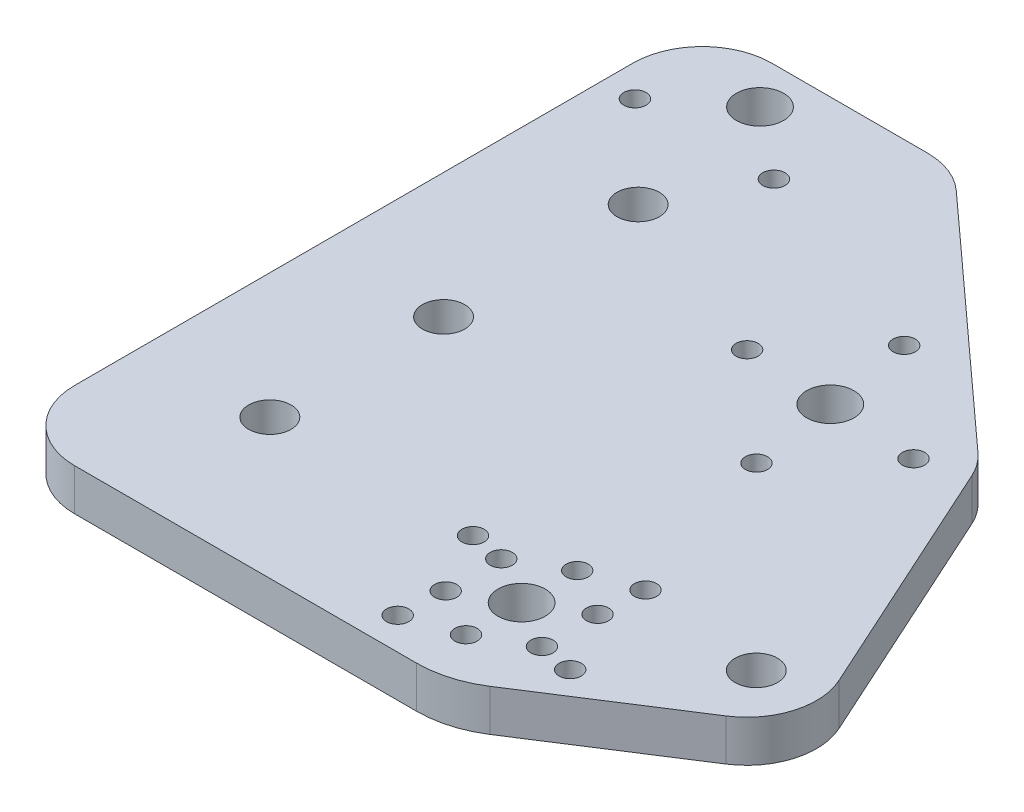
SolidWorks part; units mm, degrees
material "Policarbonato"
ref_plane "Plano frontal" through (0, 0, 0) normal (0, 0, 1) x (1, 0, 0)
ref_plane "Plano superior" through (0, 0, 0) normal (0, 1, 0) x (1, 0, 0)
ref_plane "Plano direito" through (0, 0, 0) normal (1, 0, 0) x (0, 0, -1)
ref_plane "Plano1" through (0, -6, 0) normal (0, -1, 0) x (1, 0, 0)
sketch "Esboço1" plane through (0, -6, 0) normal (0, -1, 0) x (1, 0, 0)
  line L0 (151.2357, -14.2909) -> (167.1948, 20.7865)
  line L1 (163.5005, 33.3393) -> (142.8288, 46.6294)
  line L2 (134.6661, 49.0269) -> (75.4374, 49.0269)
  line L3 (75.4374, 49.0269) -> (75.4374, -53)
  line L4 (78.4374, -56) -> (102.6847, -56)
  line L5 (109.4101, -53.4005) -> (148.859, -17.5502)
  line L6 (134.1775, -0.3541) -> (144.9383, -12.195) construction
  line L7 (144.9383, -12.195) -> (130.1372, -25.6459) construction
  line L8 (130.1372, -25.6459) -> (119.3765, -13.805) construction
  line L9 (119.3765, -13.805) -> (134.1775, -0.3541) construction
  line L10 (134.1775, -0.3541) -> (130.1372, -25.6459) construction
  line L11 (100.0374, -37) -> (80.0374, -53) construction
  line L12 (127.326, 44.4269) -> (146.5154, 38.7906) construction
  line L13 (146.5154, 38.7906) -> (142.0063, 23.4391) construction
  line L14 (142.0063, 23.4391) -> (122.8169, 29.0754) construction
  line L15 (122.8169, 29.0754) -> (127.326, 44.4269) construction
  line L16 (127.326, 44.4269) -> (142.0063, 23.4391) construction
  line L17 (134.6661, 33.933) -> (138.9199, 48.4151) construction
  line L18 (75.4374, -51.3) -> (111.7215, -51.3)
  circle A0 centre (119.3765, -13.805) radius 1.6
  circle A1 centre (146.5154, 38.7906) radius 1.6
  circle A2 centre (142.0063, 23.4391) radius 1.6
  circle A3 centre (159.9953, 25.4877) radius 3.05
  circle A4 centre (100.0374, -37) radius 1.6
  circle A5 centre (100.0374, -53) radius 1.6
  circle A6 centre (80.0374, -37) radius 1.6
  circle A7 centre (80.0374, -53) radius 1.6
  circle A8 centre (122.8169, 29.0754) radius 1.6
  circle A9 centre (127.326, 44.4269) radius 1.6
  circle A10 centre (130.1372, -25.6459) radius 1.6
  circle A11 centre (144.9383, -12.195) radius 1.6
  circle A12 centre (134.1775, -0.3541) radius 1.6
  circle A13 centre (141.5943, 29.933) radius 1.6
  circle A14 centre (134.6661, 25.933) radius 1.6
  circle A15 centre (127.7379, 29.933) radius 1.6
  circle A16 centre (127.7379, 37.933) radius 1.6
  circle A17 centre (134.6661, 41.933) radius 1.6
  circle A18 centre (141.5943, 37.933) radius 1.6
  circle A19 centre (134.6661, 33.933) radius 3.4
  circle A20 centre (132.1574, -13) radius 3.4
  circle A21 centre (90.0374, -45) radius 3.4
  arc A22 (167.1948, 20.7865) -> (163.5005, 33.3393) centre (158.0926, 24.9277) ccw
  arc A23 (142.8288, 46.6294) -> (134.6661, 49.0269) centre (134.6661, 33.933) ccw
  arc A24 (75.4374, -53) -> (78.4374, -56) centre (78.4374, -53) ccw
  arc A25 (102.6847, -56) -> (109.4101, -53.4005) centre (102.6847, -46) ccw
  arc A26 (148.859, -17.5502) -> (151.2357, -14.2909) centre (142.1335, -10.1497) ccw
  arc A27 (107.8564, -51.3) -> (114.5819, -48.7005) centre (107.8564, -41.3) ccw
  point P62 (134.6661, 33.933)
  dimension "D4" = 10
  dimension "D5" = 6.1
  dimension "D8" = 6.8
  dimension "D9" = 3.2
  dimension "D24" = 3
  dimension "D1" = 105.0269
  dimension "D2" = 11
  dimension "D3" = 82.6552
  dimension "D6" = 80.9277
  dimension "D7" = 137.736
  dimension "D10" = 20
  dimension "D11" = 16
  dimension "D12" = 6.6
  dimension "D13" = 52.897
  dimension "D14" = 43
  dimension "D15" = 16
  dimension "D16" = 90.676
  dimension "D17" = 59.2287
  dimension "D18" = 14.6
  dimension "D19" = 8
  dimension "D21" = 26.7
  dimension "D22" = 47.5
  dimension "D23" = 6.6
  dimension "D25" = 4.7
  dimension "D20" = 6
extrude "Ressalto-extrusão1" add sketch "Esboço1" against normal blind 6 contours L18 A27 L5 A26 L0 A22 L1 A23 L2 L3 A21 A19 A17 A15 A13 A11 A9 A3 A1 A0 A2 A4 A6 A8 A10 A12 A14 A16 A18 A20 region at (113.3527, -6, 3.5356)
sketch "Esboço2" plane through (0, -6, 0) normal (0, -1, 0) x (1, 0, 0)
  line L0 (75.4374, 49.0269) -> (75.4374, -51.3) construction
  line L1 (71.813, 11.433) -> (140.3089, 11.433) construction
  circle A0 centre (93.4374, 3.933) radius 3.05
  circle A1 centre (93.4374, -24.067) radius 3.05
  circle A2 centre (93.4374, 3.933) radius 7.5 construction
  circle A3 centre (93.4374, -24.067) radius 7.5 construction
  circle A4 centre (93.4374, 28.933) radius 3.05
  circle A5 centre (134.6661, 33.933) radius 3.4 construction
  dimension "D1" = 6.1
  dimension "D2" = 15
  dimension "D3" = 25
  dimension "D5" = 30
  dimension "D6" = 28
  dimension "D4" = 18
extrude "Corte-extrusão1" cut sketch "Esboço2" against normal blind 10 contours A1 | A0 | A4 region at (93.4374, -6, -24.067)
fillet "Filete1" radius 10 2 edges at (75.4374, -3, -51.3) (75.4374, -3, 49.0269)
